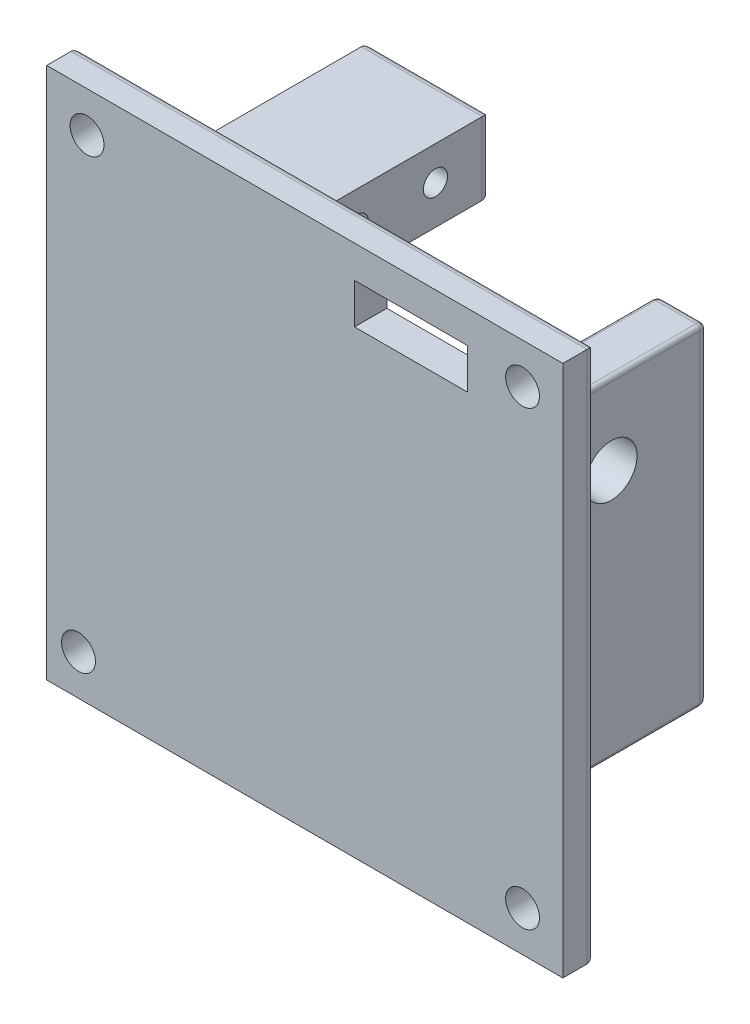
SolidWorks part; units mm, degrees
ref_plane "Front Plane" through (0, 0, 0) normal (0, 0, 1) x (1, 0, 0)
ref_plane "Top Plane" through (0, 0, 0) normal (0, 1, 0) x (1, 0, 0)
ref_plane "Right Plane" through (0, 0, 0) normal (1, 0, 0) x (0, 0, -1)
sketch "Sketch1" plane through (0, 0, 0) normal (0, 0, 1) x (1, 0, 0)
  circle A0 centre (0, 0) radius 21
  dimension "D1" = 42
extrude "Boss-Extrude1" add sketch "Sketch1" along normal blind 8
sketch "Sketch2" plane through (0, 0, 0) normal (0, 0, -1) x (-1, 0, 0)
  circle A0 centre (0, 0) radius 2
extrude "Cut-Extrude1" cut sketch "Sketch2" against normal blind 10 contours A0
sketch "Sketch4" plane through (0, 0, 0) normal (0, 0, -1) x (-1, 0, 0)
  circle A0 centre (16, 0) radius 1.1
  dimension "D1" = 16
  dimension "D3" = 2.2
  dimension "D2" = 0
sketch "Sketch5" plane through (0, 0, 0) normal (0, 0, -1) x (-1, 0, 0)
  circle A0 centre (-16, 0) radius 1.1
  dimension "D1" = 16
  dimension "D3" = 2.2
  dimension "D2" = 32
extrude "Cut-Extrude2" cut sketch "Sketch4" against normal blind 10
extrude "Cut-Extrude3" cut sketch "Sketch5" against normal blind 10
sketch "Sketch11" plane through (0, 0, 0) normal (0, 0, -1) x (-1, 0, 0)
  line L1 (-32, 33) -> (32, 33)
  line L2 (-32, 33) -> (-32, -33)
  line L3 (-32, -33) -> (32, -33)
  line L4 (32, 33) -> (32, -33)
  line L5 (-32, 33) -> (32, -33) construction
  line L6 (-32, -33) -> (32, 33) construction
  point P0 (0, 0)
  dimension "D1" = 64
  dimension "D2" = 66
extrude "Boss-Extrude3" add sketch "Sketch11" along normal blind 4
sketch "Sketch12" plane through (0, 0, -4) normal (0, 0, -1) x (-1, 0, 0)
  line L0 (32, -33) -> (32, 33) construction
  line L1 (18, -29.5) -> (3, -29.5)
  line L2 (18, -29.5) -> (18, -20.5)
  line L3 (18, -20.5) -> (3, -20.5)
  line L4 (3, -29.5) -> (3, -20.5)
  line L5 (18, -29.5) -> (3, -20.5) construction
  line L6 (18, -20.5) -> (3, -29.5) construction
  line L7 (18, 20.5) -> (3, 20.5)
  line L8 (18, 20.5) -> (18, 29.5)
  line L9 (18, 29.5) -> (3, 29.5)
  line L10 (3, 20.5) -> (3, 29.5)
  line L11 (18, 20.5) -> (3, 29.5) construction
  line L12 (18, 29.5) -> (3, 20.5) construction
  line L13 (32, 33) -> (-32, 33) construction
  line L14 (-32, -33) -> (32, -33) construction
  point P0 (10.5, -25)
  point P5 (10.5, 25)
  dimension "D1" = 41
  dimension "D2" = 3.5
  dimension "D3" = 3.5
  dimension "D4" = 9
  dimension "D5" = 15
  dimension "D6" = 15
  dimension "D7" = 14
  dimension "D8" = 14
extrude "Boss-Extrude4" add sketch "Sketch12" along normal blind 22
sketch "Sketch13" plane through (-18, 0, 0) normal (-1, 0, 0) x (0, 0, 1)
  line L0 (-26, -29.5) -> (-26, -20.5) construction
  line L1 (-26, -29.5) -> (-4, -29.5) construction
  line L2 (-26, 29.5) -> (-4, 29.5) construction
  line L3 (-26, 20.5) -> (-26, 29.5) construction
  circle A0 centre (-19.2, -25.3) radius 1.5
  circle A1 centre (-9.4, -25.3) radius 1.5
  circle A2 centre (-19.2, 25.3) radius 1.5
  circle A3 centre (-9.4, 25.3) radius 1.5
  dimension "D2" = 3
  dimension "D3" = 3
  dimension "D7" = 3
  dimension "D8" = 3
  dimension "D1" = 9.8
  dimension "D4" = 4.2
  dimension "D5" = 4.2
  dimension "D6" = 6.8
  dimension "D9" = 9.8
  dimension "D10" = 4.2
  dimension "D11" = 6.8
  dimension "D12" = 4.2
extrude "Cut-Extrude4" cut sketch "Sketch13" against normal blind 21
sketch "Sketch14" plane through (0, 0, -4) normal (0, 0, -1) x (-1, 0, 0)
  line L0 (3, 20.5) -> (18, 20.5) construction
  line L1 (-24, 20.5) -> (-18, 20.5)
  line L2 (-24, 20.5) -> (-24, -20.5)
  line L3 (-24, -20.5) -> (-18, -20.5)
  line L4 (-18, 20.5) -> (-18, -20.5)
  line L5 (-24, 20.5) -> (-18, -20.5) construction
  line L6 (-24, -20.5) -> (-18, 20.5) construction
  line L7 (18, -20.5) -> (3, -20.5) construction
  point P0 (-21, 0)
  dimension "D1" = 36
  dimension "D2" = 0
  dimension "D3" = 0
  dimension "D4" = 6
extrude "Boss-Extrude5" add sketch "Sketch14" along normal blind 22
sketch "Sketch15" plane through (18, 0, 0) normal (-1, 0, 0) x (0, 0, 1)
  line L0 (-4, -20.5) -> (-4, 20.5) construction
  line L2 (-26, 20.5) -> (-4, 20.5) construction
  circle A0 centre (-14, 10.5) radius 3.2
  dimension "D1" = 10
  dimension "D3" = 6.4
  dimension "D2" = 10
extrude "Cut-Extrude6" cut sketch "Sketch15" against normal blind 22
fillet "Fillet12" radius 1 4 edges at (0, -33, -4) (32, 0, -4) (0, 33, -4) (-32, 0, -4)
fillet "Fillet13" radius 1 12 edges at (21, -20.5, -26) (24, 0, -26) (21, 20.5, -26) (18, 0, -26) (-10.5, 29.5, -26) (-18, 25, -26) (-10.5, 20.5, -26) (-3, 25, -26) (-10.5, -20.5, -26) (-18, -25, -26) (-10.5, -29.5, -26) (-3, -25, -26)
fillet "Fillet14" radius 0.5 12 edges at (18.2929, 20.2071, -25.7071) (18.2929, -20.2071, -25.7071) (23.7071, 20.2071, -25.7071) (23.7071, -20.2071, -25.7071) (21, 20.5, -4) (18, 0, -4) (18, 20.5, -14.5) (21, -20.5, -4) (18, -20.5, -14.5) (24, 0, -4) (24, 20.5, -14.5) (24, -20.5, -14.5)
sketch "Sketch16" plane through (0, 0, -4) normal (0, 0, -1) x (-1, 0, 0)
  line L0 (31, 32) -> (-31, 32) construction
  line L1 (-20.1709, 29) -> (-6.1709, 29)
  line L2 (-20.1709, 29) -> (-20.1709, 24)
  line L3 (-20.1709, 24) -> (-6.1709, 24)
  line L4 (-6.1709, 29) -> (-6.1709, 24)
  line L5 (-20.1709, 29) -> (-6.1709, 24) construction
  line L6 (-20.1709, 24) -> (-6.1709, 29) construction
  line L7 (-31, 32) -> (-31, -32) construction
  point P0 (-13.1709, 26.5)
  point P7 (-6.1709, 26.5)
  dimension "D1" = 3
  dimension "D2" = 14
  dimension "D3" = 5
  dimension "D4" = 10.8291
extrude "Cut-Extrude7" cut sketch "Sketch16" against normal blind 22
fillet "Fillet15" radius 2.5 6 edges at (-3, 25, -4) (-18, 25, -4) (-10.5, 29.5, -4) (-3, -25, -4) (-10.5, -29.5, -4) (-18, -25, -4)
sketch "Sketch17" plane through (0, 0, 8) normal (0, 0, 1) x (1, 0, 0)
  circle A0 centre (0, 0) radius 21
extrude "Cut-Extrude9" cut sketch "Sketch17" against normal blind 8
sketch "Sketch18" plane through (0, 0, -4) normal (0, 0, -1) x (-1, 0, 0)
  line L0 (-32, 33) -> (32, 33) construction
  line L1 (32, -33) -> (-32, -33) construction
  line L2 (32, 33) -> (32, -33) construction
  line L3 (-32, -33) -> (-32, 33) construction
  circle A0 centre (-27, 28) radius 2.1
  circle A1 centre (-27, -28) radius 2.1
  circle A2 centre (28.0566, -28) radius 2.1
  circle A3 centre (27, 28) radius 2.1
  dimension "D1" = 4.2
  dimension "D2" = 4.2
  dimension "D3" = 4.2
  dimension "D4" = 4.2
  dimension "D5" = 5
  dimension "D6" = 5
  dimension "D7" = 5
  dimension "D8" = 3.9434
  dimension "D9" = 5
  dimension "D10" = 5
  dimension "D11" = 5
  dimension "D12" = 5
extrude "Cut-Extrude10" cut sketch "Sketch18" against normal blind 12
equation "\"ˋ\"=4.51731"
